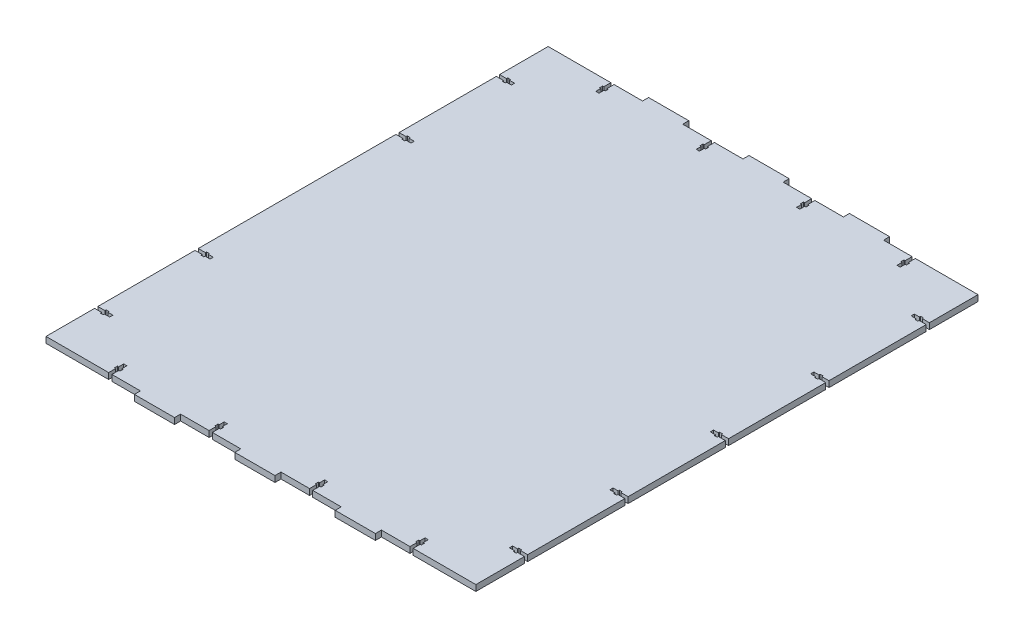
SolidWorks part; units mm, degrees
ref_plane "Front Plane" through (0, 0, 0) normal (0, 0, 1) x (1, 0, 0)
ref_plane "Top Plane" through (0, 0, 0) normal (0, 1, 0) x (1, 0, 0)
ref_plane "Right Plane" through (0, 0, 0) normal (1, 0, 0) x (0, 0, -1)
sketch "Sketch1" plane through (0, 0, 0) normal (0, 1, 0) x (1, 0, 0)
  line L1 (-214, -250) -> (214, -250)
  line L2 (-214, -250) -> (-214, 250)
  line L3 (-214, 250) -> (214, 250)
  line L4 (214, -250) -> (214, 250)
  line L5 (-214, -250) -> (214, 250) construction
  line L6 (-214, 250) -> (214, -250) construction
  point P0 (0, 0)
  dimension "D1" = 428
  dimension "D2" = 500
extrude "Boss-Extrude1" add sketch "Sketch1" along normal blind 6
sketch "Sketch2" plane through (0, 0, 0) normal (0, -1, 0) x (1, 0, 0)
  line L14 (0, 0) -> (0, 133.2527) construction
  line L15 (0, 0) -> (-145.1849, 0) construction
  line L40 (-148.4, 256) -> (-151.6, 256) construction
  line L41 (-148.4, 256) -> (-151.6, 256) construction
  line L42 (-48.4, 256) -> (-51.6, 256) construction
  line L43 (-48.4, 256) -> (-51.6, 256) construction
  line L44 (-148.4, 256) -> (-51.6, 256) construction
  line L45 (-214, 250) -> (214, 250) construction
  line L46 (-120, 256) -> (-80, 256)
  line L47 (-120, 256) -> (-120, 250)
  line L48 (-120, 250) -> (-80, 250)
  line L49 (-80, 256) -> (-80, 250)
  line L50 (-20, 250) -> (20, 250)
  line L51 (20, 256) -> (20, 250)
  line L52 (-20, 256) -> (20, 256)
  line L53 (-20, 256) -> (-20, 250)
  line L54 (80, 250) -> (120, 250)
  line L55 (120, 256) -> (120, 250)
  line L56 (80, 256) -> (120, 256)
  line L57 (80, 256) -> (80, 250)
  line L58 (120, -256) -> (120, -250)
  line L59 (80, -250) -> (120, -250)
  line L60 (80, -256) -> (120, -256)
  line L61 (80, -256) -> (80, -250)
  line L62 (20, -256) -> (20, -250)
  line L63 (-20, -256) -> (20, -256)
  line L64 (-20, -250) -> (20, -250)
  line L65 (-20, -256) -> (-20, -250)
  line L66 (-120, -250) -> (-80, -250)
  line L67 (-120, -256) -> (-120, -250)
  line L68 (-120, -256) -> (-80, -256)
  line L69 (-80, -256) -> (-80, -250)
  point P50 (-100, 256)
  dimension "D3" = 40
  dimension "D4" = 3
extrude "Boss-Extrude2" add sketch "Sketch2" against normal blind 6
sketch "Sketch3" plane through (0, 0, 0) normal (0, -1, 0) x (1, 0, 0)
  line L0 (-220, -198.4) -> (-220, -201.6) construction
  line L1 (-220, -198.4) -> (-220, -201.6)
  line L2 (-220, -200) -> (-193.4637, -200) construction
  line L3 (-214, -250) -> (-214, 250) construction
  line L4 (-199, -201.6) -> (-204, -201.6)
  line L5 (-199, -201.6) -> (-199, -198.4)
  line L6 (-199, -198.4) -> (-204, -198.4)
  line L7 (-214, -201.6) -> (-214, -198.4)
  line L8 (-199, -201.6) -> (-214, -198.4) construction
  line L9 (-199, -198.4) -> (-214, -201.6) construction
  line L10 (-207, -198.4) -> (-214, -198.4)
  line L11 (-204, -202.8) -> (-207, -202.8)
  line L12 (-204, -202.8) -> (-204, -201.6)
  line L13 (-204, -197.2) -> (-207, -197.2)
  line L14 (-207, -202.8) -> (-207, -201.6)
  line L15 (-204, -202.8) -> (-207, -197.2) construction
  line L16 (-204, -197.2) -> (-207, -202.8) construction
  line L17 (-207, -201.6) -> (-214, -201.6)
  line L18 (-199, -101.6) -> (-204, -101.6)
  line L19 (-207, -198.4) -> (-207, -197.2)
  line L20 (-204, -198.4) -> (-204, -197.2)
  line L21 (204, 202.8) -> (207, 197.2) construction
  line L22 (-199, -101.6) -> (-199, -98.4)
  line L24 (-199, -98.4) -> (-204, -98.4)
  line L25 (-214, -101.6) -> (-214, -98.4)
  line L26 (-207, -98.4) -> (-214, -98.4)
  line L27 (-204, -102.8) -> (-207, -102.8)
  line L28 (-204, -102.8) -> (-204, -101.6)
  line L29 (-204, -97.2) -> (-207, -97.2)
  line L30 (-207, -102.8) -> (-207, -101.6)
  line L31 (-207, -101.6) -> (-214, -101.6)
  line L32 (-207, -98.4) -> (-207, -97.2)
  line L33 (-204, -98.4) -> (-204, -97.2)
  line L34 (-199, -101.6) -> (-214, -98.4) construction
  line L35 (-199, -98.4) -> (-214, -101.6) construction
  line L36 (-204, -102.8) -> (-207, -97.2) construction
  line L37 (-204, -97.2) -> (-207, -102.8) construction
  line L38 (-199, -1.6) -> (-204, -1.6)
  line L39 (-199, -1.6) -> (-199, 1.6)
  line L40 (-199, 1.6) -> (-204, 1.6)
  line L41 (-214, -1.6) -> (-214, 1.6)
  line L42 (-207, 1.6) -> (-214, 1.6)
  line L43 (-204, -2.8) -> (-207, -2.8)
  line L44 (-204, -2.8) -> (-204, -1.6)
  line L45 (-204, 2.8) -> (-207, 2.8)
  line L46 (-207, -2.8) -> (-207, -1.6)
  line L47 (-207, -1.6) -> (-214, -1.6)
  line L48 (-207, 1.6) -> (-207, 2.8)
  line L49 (-204, 1.6) -> (-204, 2.8)
  line L50 (-199, -1.6) -> (-214, 1.6) construction
  line L51 (-199, 1.6) -> (-214, -1.6) construction
  line L52 (-204, -2.8) -> (-207, 2.8) construction
  line L53 (-204, 2.8) -> (-207, -2.8) construction
  line L54 (-199, 98.4) -> (-204, 98.4)
  line L55 (-199, 98.4) -> (-199, 101.6)
  line L56 (-199, 101.6) -> (-204, 101.6)
  line L57 (-214, 98.4) -> (-214, 101.6)
  line L58 (-207, 101.6) -> (-214, 101.6)
  line L59 (-204, 97.2) -> (-207, 97.2)
  line L60 (-204, 97.2) -> (-204, 98.4)
  line L61 (-204, 102.8) -> (-207, 102.8)
  line L62 (-207, 97.2) -> (-207, 98.4)
  line L63 (-207, 98.4) -> (-214, 98.4)
  line L64 (-207, 101.6) -> (-207, 102.8)
  line L65 (-204, 101.6) -> (-204, 102.8)
  line L66 (-199, 98.4) -> (-214, 101.6) construction
  line L67 (-199, 101.6) -> (-214, 98.4) construction
  line L68 (-204, 97.2) -> (-207, 102.8) construction
  line L69 (-204, 102.8) -> (-207, 97.2) construction
  line L70 (-199, 198.4) -> (-204, 198.4)
  line L71 (-199, 198.4) -> (-199, 201.6)
  line L72 (-199, 201.6) -> (-204, 201.6)
  line L73 (-214, 198.4) -> (-214, 201.6)
  line L74 (-207, 201.6) -> (-214, 201.6)
  line L75 (-204, 197.2) -> (-207, 197.2)
  line L76 (-204, 197.2) -> (-204, 198.4)
  line L77 (-204, 202.8) -> (-207, 202.8)
  line L78 (-207, 197.2) -> (-207, 198.4)
  line L79 (-207, 198.4) -> (-214, 198.4)
  line L80 (-207, 201.6) -> (-207, 202.8)
  line L81 (-204, 201.6) -> (-204, 202.8)
  line L82 (-199, 198.4) -> (-214, 201.6) construction
  line L83 (-199, 201.6) -> (-214, 198.4) construction
  line L84 (-204, 197.2) -> (-207, 202.8) construction
  line L85 (-204, 202.8) -> (-207, 197.2) construction
  line L86 (0, 0) -> (0, 128.8409) construction
  line L87 (204, 197.2) -> (207, 202.8) construction
  line L88 (199, 201.6) -> (214, 198.4) construction
  line L89 (199, 198.4) -> (214, 201.6) construction
  line L90 (204, 102.8) -> (207, 97.2) construction
  line L91 (204, 97.2) -> (207, 102.8) construction
  line L92 (199, 101.6) -> (214, 98.4) construction
  line L93 (199, 98.4) -> (214, 101.6) construction
  line L94 (204, 2.8) -> (207, -2.8) construction
  line L95 (204, -2.8) -> (207, 2.8) construction
  line L96 (199, 1.6) -> (214, -1.6) construction
  line L97 (199, -1.6) -> (214, 1.6) construction
  line L98 (204, -97.2) -> (207, -102.8) construction
  line L99 (204, -102.8) -> (207, -97.2) construction
  line L100 (199, -98.4) -> (214, -101.6) construction
  line L101 (199, -101.6) -> (214, -98.4) construction
  line L102 (204, -197.2) -> (207, -202.8) construction
  line L103 (204, -202.8) -> (207, -197.2) construction
  line L104 (199, -198.4) -> (214, -201.6) construction
  line L105 (199, -201.6) -> (214, -198.4) construction
  line L106 (204, 201.6) -> (204, 202.8)
  line L107 (207, 201.6) -> (207, 202.8)
  line L108 (207, 198.4) -> (214, 198.4)
  line L109 (207, 197.2) -> (207, 198.4)
  line L110 (204, 202.8) -> (207, 202.8)
  line L111 (204, 197.2) -> (204, 198.4)
  line L112 (204, 197.2) -> (207, 197.2)
  line L113 (207, 201.6) -> (214, 201.6)
  line L114 (214, 198.4) -> (214, 201.6)
  line L115 (199, 201.6) -> (204, 201.6)
  line L116 (199, 198.4) -> (199, 201.6)
  line L117 (199, 198.4) -> (204, 198.4)
  line L118 (204, 101.6) -> (204, 102.8)
  line L119 (207, 101.6) -> (207, 102.8)
  line L120 (207, 98.4) -> (214, 98.4)
  line L121 (207, 97.2) -> (207, 98.4)
  line L122 (204, 102.8) -> (207, 102.8)
  line L123 (204, 97.2) -> (204, 98.4)
  line L124 (204, 97.2) -> (207, 97.2)
  line L125 (207, 101.6) -> (214, 101.6)
  line L126 (214, 98.4) -> (214, 101.6)
  line L127 (199, 101.6) -> (204, 101.6)
  line L128 (199, 98.4) -> (199, 101.6)
  line L129 (199, 98.4) -> (204, 98.4)
  line L130 (204, 1.6) -> (204, 2.8)
  line L131 (207, 1.6) -> (207, 2.8)
  line L132 (207, -1.6) -> (214, -1.6)
  line L133 (207, -2.8) -> (207, -1.6)
  line L134 (204, 2.8) -> (207, 2.8)
  line L135 (204, -2.8) -> (204, -1.6)
  line L136 (204, -2.8) -> (207, -2.8)
  line L137 (207, 1.6) -> (214, 1.6)
  line L138 (214, -1.6) -> (214, 1.6)
  line L139 (199, 1.6) -> (204, 1.6)
  line L140 (199, -1.6) -> (199, 1.6)
  line L141 (199, -1.6) -> (204, -1.6)
  line L142 (204, -98.4) -> (204, -97.2)
  line L143 (207, -98.4) -> (207, -97.2)
  line L144 (207, -101.6) -> (214, -101.6)
  line L145 (207, -102.8) -> (207, -101.6)
  line L146 (204, -97.2) -> (207, -97.2)
  line L147 (204, -102.8) -> (204, -101.6)
  line L148 (204, -102.8) -> (207, -102.8)
  line L149 (207, -98.4) -> (214, -98.4)
  line L150 (214, -101.6) -> (214, -98.4)
  line L151 (199, -98.4) -> (204, -98.4)
  line L152 (199, -101.6) -> (199, -98.4)
  line L153 (204, -198.4) -> (204, -197.2)
  line L154 (207, -198.4) -> (207, -197.2)
  line L155 (199, -101.6) -> (204, -101.6)
  line L156 (207, -201.6) -> (214, -201.6)
  line L157 (207, -202.8) -> (207, -201.6)
  line L158 (204, -197.2) -> (207, -197.2)
  line L159 (204, -202.8) -> (204, -201.6)
  line L160 (204, -202.8) -> (207, -202.8)
  line L161 (207, -198.4) -> (214, -198.4)
  line L162 (214, -201.6) -> (214, -198.4)
  line L163 (199, -198.4) -> (204, -198.4)
  line L164 (199, -201.6) -> (199, -198.4)
  line L165 (199, -201.6) -> (204, -201.6)
  line L166 (-151.6, -256) -> (-148.4, -256) construction
  line L167 (-151.6, -256) -> (-148.4, -256) construction
  line L168 (-150, -256) -> (-150, -234.6121) construction
  line L169 (-120, -250) -> (-214, -250) construction
  line L170 (-151.6, -235) -> (-148.4, -235)
  line L171 (-151.6, -235) -> (-151.6, -240)
  line L172 (-151.6, -250) -> (-148.4, -250)
  line L173 (-148.4, -235) -> (-148.4, -240)
  line L174 (-151.6, -235) -> (-148.4, -250) construction
  line L175 (-151.6, -250) -> (-148.4, -235) construction
  line L176 (-148.4, -243) -> (-147.2, -243)
  line L177 (-152.8, -243) -> (-151.6, -243)
  line L178 (-152.8, -243) -> (-152.8, -240)
  line L179 (-152.8, -240) -> (-151.6, -240)
  line L180 (-147.2, -243) -> (-147.2, -240)
  line L181 (-152.8, -243) -> (-147.2, -240) construction
  line L182 (-152.8, -240) -> (-147.2, -243) construction
  line L183 (-151.6, -243) -> (-151.6, -250)
  line L184 (-148.4, -243) -> (-148.4, -250)
  line L185 (-148.4, -240) -> (-147.2, -240)
  line L186 (-51.6, -235) -> (-48.4, -235)
  line L187 (-51.6, -235) -> (-51.6, -240)
  line L188 (-51.6, -250) -> (-48.4, -250)
  line L189 (-48.4, -235) -> (-48.4, -240)
  line L190 (-48.4, -243) -> (-47.2, -243)
  line L191 (-52.8, -243) -> (-51.6, -243)
  line L192 (-52.8, -243) -> (-52.8, -240)
  line L193 (-52.8, -240) -> (-51.6, -240)
  line L194 (-47.2, -243) -> (-47.2, -240)
  line L195 (-51.6, -243) -> (-51.6, -250)
  line L196 (-48.4, -243) -> (-48.4, -250)
  line L197 (-48.4, -240) -> (-47.2, -240)
  line L198 (-51.6, -235) -> (-48.4, -250) construction
  line L199 (-51.6, -250) -> (-48.4, -235) construction
  line L200 (-52.8, -243) -> (-47.2, -240) construction
  line L201 (-52.8, -240) -> (-47.2, -243) construction
  line L202 (48.4, -235) -> (51.6, -235)
  line L203 (48.4, -235) -> (48.4, -240)
  line L204 (48.4, -250) -> (51.6, -250)
  line L205 (51.6, -235) -> (51.6, -240)
  line L206 (51.6, -243) -> (52.8, -243)
  line L207 (47.2, -243) -> (48.4, -243)
  line L208 (47.2, -243) -> (47.2, -240)
  line L209 (47.2, -240) -> (48.4, -240)
  line L210 (52.8, -243) -> (52.8, -240)
  line L211 (48.4, -243) -> (48.4, -250)
  line L212 (51.6, -243) -> (51.6, -250)
  line L213 (51.6, -240) -> (52.8, -240)
  line L214 (48.4, -235) -> (51.6, -250) construction
  line L215 (48.4, -250) -> (51.6, -235) construction
  line L216 (47.2, -243) -> (52.8, -240) construction
  line L217 (47.2, -240) -> (52.8, -243) construction
  line L218 (148.4, -235) -> (151.6, -235)
  line L219 (148.4, -235) -> (148.4, -240)
  line L220 (148.4, -250) -> (151.6, -250)
  line L221 (151.6, -235) -> (151.6, -240)
  line L222 (151.6, -243) -> (152.8, -243)
  line L223 (147.2, -243) -> (148.4, -243)
  line L224 (147.2, -243) -> (147.2, -240)
  line L225 (147.2, -240) -> (148.4, -240)
  line L226 (152.8, -243) -> (152.8, -240)
  line L227 (148.4, -243) -> (148.4, -250)
  line L228 (151.6, -243) -> (151.6, -250)
  line L229 (151.6, -240) -> (152.8, -240)
  line L230 (148.4, -235) -> (151.6, -250) construction
  line L231 (148.4, -250) -> (151.6, -235) construction
  line L232 (147.2, -243) -> (152.8, -240) construction
  line L233 (147.2, -240) -> (152.8, -243) construction
  line L234 (0, 0) -> (96.8105, 0) construction
  line L235 (147.2, 240) -> (152.8, 243) construction
  line L236 (147.2, 243) -> (152.8, 240) construction
  line L237 (148.4, 250) -> (151.6, 235) construction
  line L238 (148.4, 235) -> (151.6, 250) construction
  line L239 (47.2, 240) -> (52.8, 243) construction
  line L240 (47.2, 243) -> (52.8, 240) construction
  line L241 (48.4, 250) -> (51.6, 235) construction
  line L242 (48.4, 235) -> (51.6, 250) construction
  line L243 (-52.8, 240) -> (-47.2, 243) construction
  line L244 (-52.8, 243) -> (-47.2, 240) construction
  line L245 (-51.6, 250) -> (-48.4, 235) construction
  line L246 (-51.6, 235) -> (-48.4, 250) construction
  line L247 (-152.8, 240) -> (-147.2, 243) construction
  line L248 (-152.8, 243) -> (-147.2, 240) construction
  line L249 (-151.6, 250) -> (-148.4, 235) construction
  line L250 (-151.6, 235) -> (-148.4, 250) construction
  line L251 (151.6, 240) -> (152.8, 240)
  line L252 (151.6, 243) -> (151.6, 250)
  line L253 (148.4, 243) -> (148.4, 250)
  line L254 (152.8, 243) -> (152.8, 240)
  line L255 (147.2, 240) -> (148.4, 240)
  line L256 (147.2, 243) -> (147.2, 240)
  line L257 (147.2, 243) -> (148.4, 243)
  line L258 (151.6, 243) -> (152.8, 243)
  line L259 (151.6, 235) -> (151.6, 240)
  line L260 (148.4, 250) -> (151.6, 250)
  line L261 (148.4, 235) -> (148.4, 240)
  line L262 (148.4, 235) -> (151.6, 235)
  line L263 (51.6, 240) -> (52.8, 240)
  line L264 (51.6, 243) -> (51.6, 250)
  line L265 (48.4, 243) -> (48.4, 250)
  line L266 (52.8, 243) -> (52.8, 240)
  line L267 (47.2, 240) -> (48.4, 240)
  line L268 (47.2, 243) -> (47.2, 240)
  line L269 (47.2, 243) -> (48.4, 243)
  line L270 (51.6, 243) -> (52.8, 243)
  line L271 (51.6, 235) -> (51.6, 240)
  line L272 (48.4, 250) -> (51.6, 250)
  line L273 (48.4, 235) -> (48.4, 240)
  line L274 (48.4, 235) -> (51.6, 235)
  line L275 (-48.4, 240) -> (-47.2, 240)
  line L276 (-48.4, 243) -> (-48.4, 250)
  line L277 (-51.6, 243) -> (-51.6, 250)
  line L278 (-47.2, 243) -> (-47.2, 240)
  line L279 (-52.8, 240) -> (-51.6, 240)
  line L280 (-52.8, 243) -> (-52.8, 240)
  line L281 (-52.8, 243) -> (-51.6, 243)
  line L282 (-48.4, 243) -> (-47.2, 243)
  line L283 (-48.4, 235) -> (-48.4, 240)
  line L284 (-51.6, 250) -> (-48.4, 250)
  line L285 (-51.6, 235) -> (-51.6, 240)
  line L286 (-51.6, 235) -> (-48.4, 235)
  line L287 (-148.4, 240) -> (-147.2, 240)
  line L288 (-148.4, 243) -> (-148.4, 250)
  line L289 (-151.6, 243) -> (-151.6, 250)
  line L290 (-147.2, 243) -> (-147.2, 240)
  line L291 (-152.8, 240) -> (-151.6, 240)
  line L292 (-152.8, 243) -> (-152.8, 240)
  line L293 (-152.8, 243) -> (-151.6, 243)
  line L294 (-148.4, 243) -> (-147.2, 243)
  line L295 (-148.4, 235) -> (-148.4, 240)
  line L296 (-151.6, 250) -> (-148.4, 250)
  line L297 (-151.6, 235) -> (-151.6, 240)
  line L298 (-151.6, 235) -> (-148.4, 235)
  point P4 (-206.5, -200)
  point P11 (-205.5, -200)
  point P25 (-206.5, -100)
  point P31 (-205.5, -100)
  point P40 (-206.5, 0)
  point P45 (-205.5, 0)
  point P54 (-206.5, 100)
  point P59 (-205.5, 100)
  point P68 (-206.5, 200)
  point P73 (-205.5, 200)
  point P140 (205.5, 200)
  point P141 (206.5, 200)
  point P142 (205.5, 100)
  point P143 (206.5, 100)
  point P144 (205.5, 0)
  point P145 (206.5, 0)
  point P146 (205.5, -100)
  point P147 (206.5, -100)
  point P148 (205.5, -200)
  point P149 (206.5, -200)
  point P154 (-150, -242.5)
  point P161 (-150, -241.5)
  point P171 (-50, -242.5)
  point P176 (-50, -241.5)
  point P185 (50, -242.5)
  point P190 (50, -241.5)
  point P199 (150, -242.5)
  point P204 (150, -241.5)
  point P261 (150, 241.5)
  point P262 (150, 242.5)
  point P263 (50, 241.5)
  point P264 (50, 242.5)
  point P265 (-50, 241.5)
  point P266 (-50, 242.5)
  point P267 (-150, 241.5)
  point P268 (-150, 242.5)
  line M5 (214, -250) -> (214, 250)
  line M6 (214, 250) -> (120, 250)
  line M10 (80, 250) -> (20, 250)
  line M14 (-20, 250) -> (-80, 250)
  line M18 (-120, 250) -> (-214, 250)
  line M19 (-214, 250) -> (-214, -250)
  line M20 (-214, -250) -> (-120, -250)
  line M24 (-80, -250) -> (-20, -250)
  line M28 (20, -250) -> (80, -250)
  line M32 (120, -250) -> (214, -250)
  dimension "D1" = 15
  dimension "D2" = 3
  dimension "D3" = 7
  dimension "D4" = 5.6
  dimension "D5" = 5
  dimension "D6" = 15
  dimension "D7" = 5.6
  dimension "D8" = 7
  dimension "D9" = 4
extrude "Cut-Extrude1" cut sketch "Sketch3" against normal through all contours L297 L298 L295 L287 L290 L294 L288 L289 L293 L292 L291 M18 | L285 L286 L283 L275 L278 L282 L276 L277 L281 L280 L279 M14 | L261 L262 L259 L251 L254 L258 L252 L253 L257 L256 L255 M6 | L116 L117 L111 L112 L109 L108 L113 L107 L110 L106 L115 M5 | L128 L129 L123 L124 L121 L120 L125 L119 L122 L118 L127 M5 | L140 L141 L135 L136 L133 L132 L137 L131 L134 L130 L139 M5 | L152 L155 L147 L148 L145 L144 L149 L143 L146 L142 L151 M5 | L164 L165 L159 L160 L157 L156 L161 L154 L158 L153 L163 M5 | L229 L221 L218 L219 L225 L224 L223 L227 L228 L222 L226 M32 | L213 L205 L202 L203 L209 L208 L207 L211 L212 L206 L210 M28 | L197 L189 L186 L187 L193 L192 L191 L195 L196 L190 L194 M24 | L185 L173 L170 L171 L179 L178 L177 L183 L184 L176 L180 M20 | L6 L20 L13 L19 L10 L17 L14 L11 L12 L4 L5 M19 | L24 L33 L29 L32 L26 L31 L30 L27 L28 L18 L22 M19 | L72 L81 L77 L80 L74 L79 L78 L75 L76 L70 L71 M19 | L273 L274 L271 L263 L266 L270 L264 L265 L269 L268 L267 M10 | L56 L65 L61 L64 L58 L57 L63 L62 L59 L60 L54 L55 region at (-150, 0, -242.3696) region at (-150, 0, 242.3696) region at (-206.3696, 0, 200) region at (-206.3696, 0, -100) region at (-206.3696, 0, -200) region at (150, 0, 242.3696) region at (150, 0, -242.3696) region at (206.3696, 0, -200) region at (206.3696, 0, -100) region at (206.3696, 0, 0) region at (206.3696, 0, 100) region at (206.3696, 0, 200) region at (-50, 0, -242.3696) region at (50, 0, -242.3696) region at (50, 0, 242.3696) region at (-50, 0, 242.3696)
